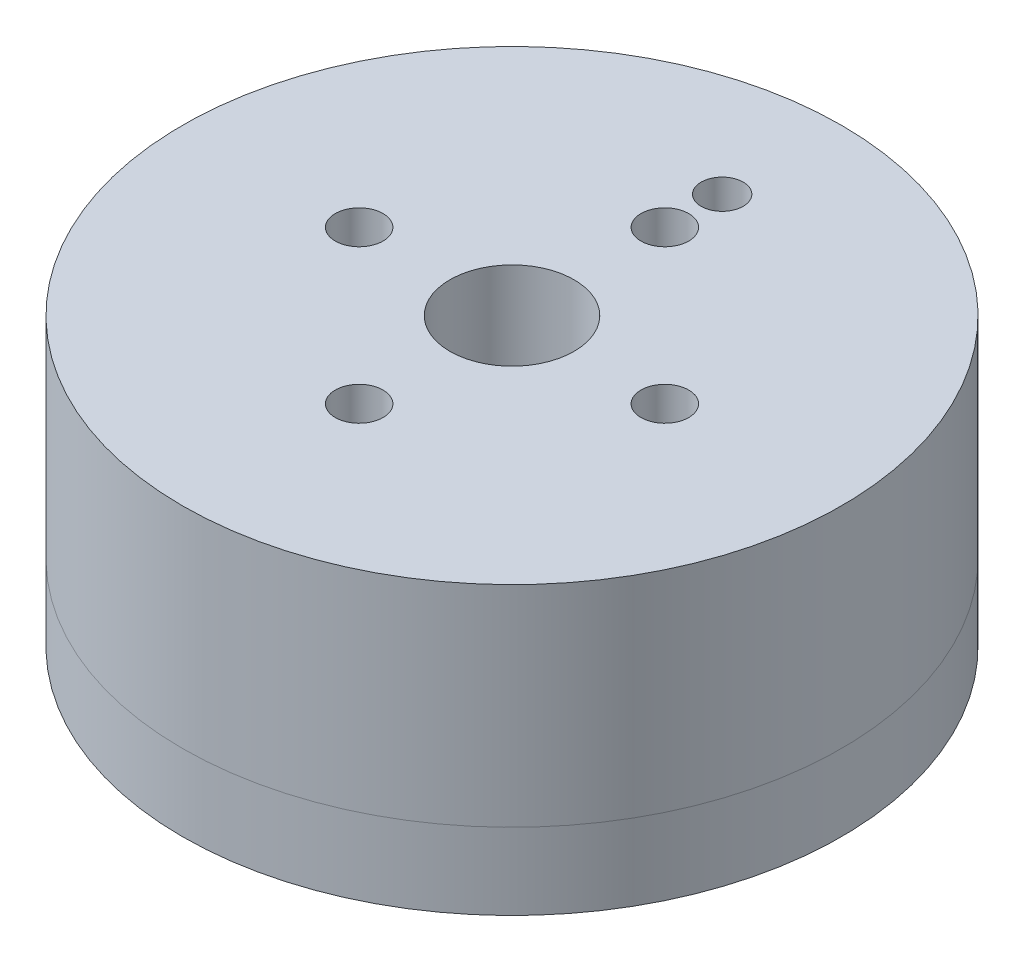
SolidWorks part; units mm, degrees
ref_plane "Front Plane" through (0, 0, 0) normal (0, 0, 1) x (1, 0, 0)
ref_plane "Top Plane" through (0, 0, 0) normal (0, 1, 0) x (1, 0, 0)
ref_plane "Right Plane" through (0, 0, 0) normal (1, 0, 0) x (0, 0, -1)
sketch "Sketch1" plane through (0, 0, 0) normal (0, 1, 0) x (1, 0, 0)
  circle A0 centre (0, 0) radius 17.25
  dimension "D1" = 34.5
extrude "Boss-Extrude1" add sketch "Sketch1" along normal blind 11
sketch "Sketch2" plane through (0, 11, 0) normal (0, 1, 0) x (1, 0, 0)
  circle A0 centre (0, 0) radius 8 construction
  circle A2 centre (0, 8) radius 1.25
  circle A3 centre (0, 11) radius 1.1
  circle A4 centre (8, 0) radius 1.25
  circle A5 centre (0, 0) radius 8 construction
  circle A6 centre (0, -8) radius 1.25
  circle A7 centre (0, 0) radius 8 construction
  circle A8 centre (-8, 0) radius 1.25
  circle A9 centre (0, 0) radius 8 construction
  point P20 (0, 0)
  dimension "D1" = 16
  dimension "D2" = 2.5
  dimension "D3" = 2.2
  dimension "D6" = 3
  dimension "D5" = 4
extrude "Cut-Extrude1" cut sketch "Sketch2" against normal blind 3
extrude "Boss-Extrude2" add sketch "Sketch1<2>" against normal blind 4 separate body
sketch "Sketch1<2>" plane through (0, 0, 0) normal (0, 1, 0) x (1, 0, 0) same geometry as "Sketch1"
sketch "Sketch4" plane through (0, -4, 0) normal (0, -1, 0) x (1, 0, 0)
  line L0 (-17.25, 0) -> (17.25, 0) construction
  line L2 (0, 17.25) -> (0, -17.25) construction
  line L3 (-6.7, 6.7) -> (6.7, 6.7) construction
  line L4 (-6.7, 6.7) -> (-6.7, -6.7) construction
  line L5 (-6.7, -6.7) -> (6.7, -6.7) construction
  line L6 (6.7, 6.7) -> (6.7, -6.7) construction
  line L7 (-6.7, 6.7) -> (6.7, -6.7) construction
  line L8 (-6.7, -6.7) -> (6.7, 6.7) construction
  circle A0 centre (0, 0) radius 17.25 construction
  circle A2 centre (-6.7, 6.7) radius 1.25
  circle A3 centre (6.7, 6.7) radius 1.25
  circle A4 centre (6.7, -6.7) radius 1.25
  circle A5 centre (-6.7, -6.7) radius 1.25
  circle A6 centre (13.1674, 0) radius 1.1
  point P7 (0, 0)
  point P15 (0, 0)
  dimension "D3" = 2.5
  dimension "D6" = 2.2
  dimension "D1" = 13.4
  dimension "D2" = 13.4
  dimension "D4" = 2
  dimension "D5" = 2
extrude "Cut-Extrude3" cut sketch "Sketch4" against normal blind 4
sketch "Sketch5" plane through (0, -4, 0) normal (0, -1, 0) x (1, 0, 0)
  circle A0 centre (0, 0) radius 5
  circle A1 centre (0, 0) radius 6
  circle A2 centre (0, 0) radius 2.7
  dimension "D1" = 10
  dimension "D2" = 12
  dimension "D3" = 5.4
extrude "Boss-Extrude3" add sketch "Sketch5" along normal blind 4.5 contours A0
extrude "Boss-Extrude4" add sketch "Sketch5<3>" against normal blind 2.5 from surface contours A1 A0 region at (-5.8303, -4, 0) starting at face at (0, -8.5, -5)
sketch "Sketch5<3>" plane through (0, -4, 0) normal (0, -1, 0) x (1, 0, 0) same geometry as "Sketch5"
extrude "Cut-Extrude4" cut sketch "Sketch5<5>" against normal up to surface (-2 mm away) from surface contours A2 up to face at (0, -6, -5) starting at face at (0, -8.5, -6)
sketch "Sketch5<5>" plane through (0, -4, 0) normal (0, -1, 0) x (1, 0, 0) same geometry as "Sketch5"
sketch "Sketch6" plane through (0, 0, 0) normal (0, 1, 0) x (1, 0, 0)
  circle A0 centre (0, 0) radius 3.25
  dimension "D1" = 6.5
extrude "Cut-Extrude5" cut sketch "Sketch6" along normal up to surface (11 mm away) and the other way up to surface (6 mm away) up to face at (0, 11, -9.9) other way up to face at (0, -6, -5)
fillet "Fillet1" radius 2 1 edges at (0, -6, -5) first distance on face at (0, -4, 5)
